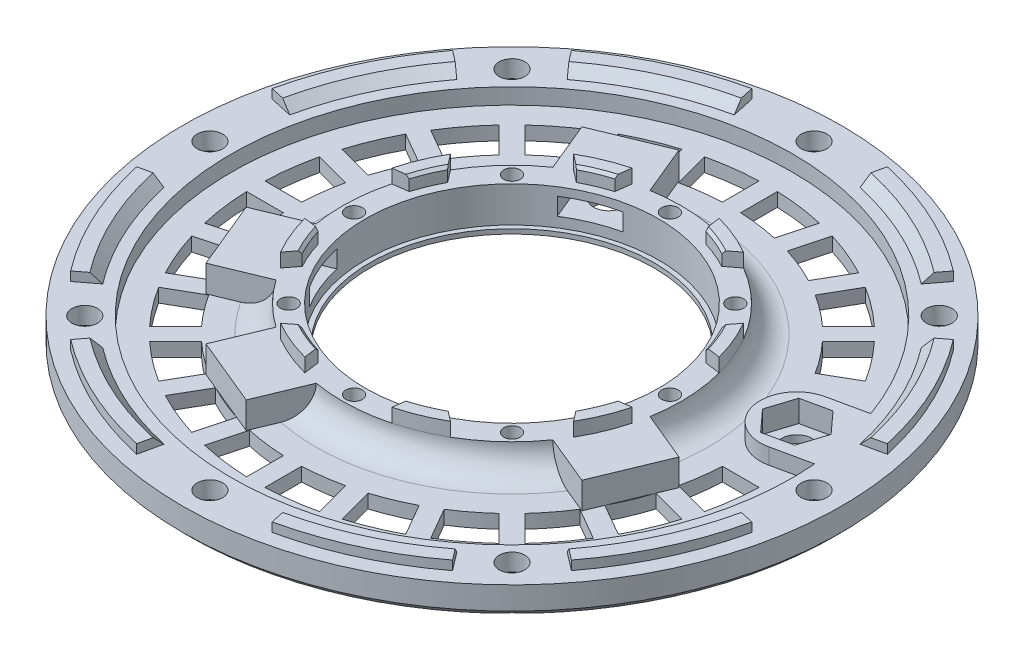
SolidWorks part; units mm, degrees
ref_plane "Front Plane" through (0, 0, 0) normal (0, 0, 1) x (1, 0, 0)
ref_plane "Top Plane" through (0, 0, 0) normal (0, 1, 0) x (1, 0, 0)
ref_plane "Right Plane" through (0, 0, 0) normal (1, 0, 0) x (0, 0, -1)
sketch "Sketch1" plane through (0, 0, 0) normal (0, 1, 0) x (1, 0, 0)
  circle A0 centre (0, 0) radius 16.025
  circle A1 centre (0, 0) radius 36
  dimension "D1" = 32.05
  dimension "D2" = 72
extrude "Boss-Extrude1" add sketch "Sketch1" along normal blind 1
sketch "Sketch2" plane through (0, 0, 0) normal (0, -1, 0) x (1, 0, 0)
  circle A0 centre (0, 0) radius 17.25 construction
  circle A1 centre (0, 0) radius 18.5 construction
  circle A2 centre (0, 0) radius 18.5
  circle A3 centre (0, 0) radius 16.025 construction
  circle A4 centre (0, 0) radius 16.025
  arc A5 (-1.2, 18.461) -> (-4.705, 17.8917) centre (0, 0) ccw construction
  point P3 (0, -17.25)
extrude "Boss-Extrude2" add sketch "Sketch2" against normal offset from surface (3.9 mm away) 3.9 up to face at (0, 0, 36)
fillet "Fillet1" radius 2.9 1 edges at (0, 1, 18.5)
sketch "Sketch4" plane through (0, 0, 0) normal (0, 1, 0) x (1, 0, 0)
  circle A0 centre (0, 0) radius 15.525
  circle A1 centre (0, 0) radius 36
  circle A2 centre (0, 0) radius 36
  circle A3 centre (0, 0) radius 16.025 construction
  dimension "D2" = 0.5
  dimension "D1" = 0
extrude "Boss-Extrude3" add sketch "Sketch4" against normal blind 0.5
sketch "Sketch5" plane through (0, 1, 0) normal (0, 1, 0) x (1, 0, 0)
  line L0 (27.99, -0.75) -> (19.9859, -0.75) construction
  line L1 (19.9859, 0.75) -> (27.99, 0.75) construction
  line L2 (27.99, -0.75) -> (19.9859, -0.75) construction
  line L3 (19.9859, 0.75) -> (27.99, 0.75) construction
  line L4 (0, 0) -> (36, 0) construction
  line L5 (0, 0) -> (34.7733, 9.3175) construction
  line L6 (34.7733, 9.3175) -> (36, 0) construction
  line L7 (0, 0) -> (35.3867, 4.6587) construction
  line L8 (27.99, 1) -> (23.9792, 1)
  line L9 (27.295, 6.2784) -> (23.4209, 5.2403)
  line L10 (27.99, -1) -> (23.9792, -1)
  line L11 (27.295, -6.2784) -> (23.4209, -5.2403)
  line L12 (26.7774, -8.2103) -> (22.9033, -7.1722)
  line L13 (24.74, -13.129) -> (21.2666, -11.1236)
  line L14 (23.74, -14.861) -> (20.2666, -12.8556)
  line L15 (20.499, -19.0848) -> (17.6629, -16.2487)
  line L16 (19.0848, -20.499) -> (16.2487, -17.6629)
  line L17 (14.861, -23.74) -> (12.8556, -20.2666)
  line L18 (13.129, -24.74) -> (11.1236, -21.2666)
  line L19 (8.2103, -26.7774) -> (7.1722, -22.9033)
  line L20 (6.2784, -27.295) -> (5.2403, -23.4209)
  line L21 (1, -27.99) -> (1, -23.9792)
  line L22 (-1, -27.99) -> (-1, -23.9792)
  line L23 (-6.2784, -27.295) -> (-5.2403, -23.4209)
  line L24 (-8.2103, -26.7774) -> (-7.1722, -22.9033)
  line L25 (-13.129, -24.74) -> (-11.1236, -21.2666)
  line L26 (-14.861, -23.74) -> (-12.8556, -20.2666)
  line L27 (-19.0848, -20.499) -> (-16.2487, -17.6629)
  line L28 (-20.499, -19.0848) -> (-17.6629, -16.2487)
  line L29 (-23.74, -14.861) -> (-20.2666, -12.8556)
  line L30 (-24.74, -13.129) -> (-21.2666, -11.1236)
  line L31 (-26.7774, -8.2103) -> (-22.9033, -7.1722)
  line L32 (-27.295, -6.2784) -> (-23.4209, -5.2403)
  line L33 (-27.99, -1) -> (-23.9792, -1)
  line L34 (-27.99, 1) -> (-23.9792, 1)
  line L35 (-27.295, 6.2784) -> (-23.4209, 5.2403)
  line L36 (-26.7774, 8.2103) -> (-22.9033, 7.1722)
  line L37 (-24.74, 13.129) -> (-21.2666, 11.1236)
  line L38 (-23.74, 14.861) -> (-20.2666, 12.8556)
  line L39 (-20.499, 19.0848) -> (-17.6629, 16.2487)
  line L40 (-19.0848, 20.499) -> (-16.2487, 17.6629)
  line L41 (-14.861, 23.74) -> (-12.8556, 20.2666)
  line L42 (-13.129, 24.74) -> (-11.1236, 21.2666)
  line L43 (-8.2103, 26.7774) -> (-7.1722, 22.9033)
  line L44 (-6.2784, 27.295) -> (-5.2403, 23.4209)
  line L45 (-1, 27.99) -> (-1, 23.9792)
  line L46 (1, 27.99) -> (1, 23.9792)
  line L47 (6.2784, 27.295) -> (5.2403, 23.4209)
  line L48 (8.2103, 26.7774) -> (7.1722, 22.9033)
  line L49 (13.129, 24.74) -> (11.1236, 21.2666)
  line L50 (14.861, 23.74) -> (12.8556, 20.2666)
  line L51 (19.0848, 20.499) -> (16.2487, 17.6629)
  line L52 (20.499, 19.0848) -> (17.6629, 16.2487)
  line L53 (23.74, 14.861) -> (20.2666, 12.8556)
  line L54 (24.74, 13.129) -> (21.2666, 11.1236)
  line L55 (26.7774, 8.2103) -> (22.9033, 7.1722)
  line L56 (0, 0) -> (23.9792, 1) construction
  circle A0 centre (0, 0) radius 24 construction
  circle A2 centre (0, 0) radius 36 construction
  arc A3 (23.9792, 1) -> (23.4209, 5.2403) centre (0, 0) ccw
  arc A4 (27.99, 1) -> (27.295, 6.2784) centre (0, 0) ccw
  arc A5 (27.295, -6.2784) -> (27.99, -1) centre (0, 0) ccw
  arc A6 (23.4209, -5.2403) -> (23.9792, -1) centre (0, 0) ccw
  arc A7 (24.74, -13.129) -> (26.7774, -8.2103) centre (0, 0) ccw
  arc A8 (21.2666, -11.1236) -> (22.9033, -7.1722) centre (0, 0) ccw
  arc A9 (20.499, -19.0848) -> (23.74, -14.861) centre (0, 0) ccw
  arc A10 (17.6629, -16.2487) -> (20.2666, -12.8556) centre (0, 0) ccw
  arc A11 (14.861, -23.74) -> (19.0848, -20.499) centre (0, 0) ccw
  arc A12 (12.8556, -20.2666) -> (16.2487, -17.6629) centre (0, 0) ccw
  arc A13 (8.2103, -26.7774) -> (13.129, -24.74) centre (0, 0) ccw
  arc A14 (7.1722, -22.9033) -> (11.1236, -21.2666) centre (0, 0) ccw
  arc A15 (1, -27.99) -> (6.2784, -27.295) centre (0, 0) ccw
  arc A16 (1, -23.9792) -> (5.2403, -23.4209) centre (0, 0) ccw
  arc A17 (-6.2784, -27.295) -> (-1, -27.99) centre (0, 0) ccw
  arc A18 (-5.2403, -23.4209) -> (-1, -23.9792) centre (0, 0) ccw
  arc A19 (-13.129, -24.74) -> (-8.2103, -26.7774) centre (0, 0) ccw
  arc A20 (-11.1236, -21.2666) -> (-7.1722, -22.9033) centre (0, 0) ccw
  arc A21 (-19.0848, -20.499) -> (-14.861, -23.74) centre (0, 0) ccw
  arc A22 (-16.2487, -17.6629) -> (-12.8556, -20.2666) centre (0, 0) ccw
  arc A23 (-23.74, -14.861) -> (-20.499, -19.0848) centre (0, 0) ccw
  arc A24 (-20.2666, -12.8556) -> (-17.6629, -16.2487) centre (0, 0) ccw
  arc A25 (-26.7774, -8.2103) -> (-24.74, -13.129) centre (0, 0) ccw
  arc A26 (-22.9033, -7.1722) -> (-21.2666, -11.1236) centre (0, 0) ccw
  arc A27 (-27.99, -1) -> (-27.295, -6.2784) centre (0, 0) ccw
  arc A28 (-23.9792, -1) -> (-23.4209, -5.2403) centre (0, 0) ccw
  arc A29 (-27.295, 6.2784) -> (-27.99, 1) centre (0, 0) ccw
  arc A30 (-23.4209, 5.2403) -> (-23.9792, 1) centre (0, 0) ccw
  arc A31 (-24.74, 13.129) -> (-26.7774, 8.2103) centre (0, 0) ccw
  arc A32 (-21.2666, 11.1236) -> (-22.9033, 7.1722) centre (0, 0) ccw
  arc A33 (-20.499, 19.0848) -> (-23.74, 14.861) centre (0, 0) ccw
  arc A34 (-17.6629, 16.2487) -> (-20.2666, 12.8556) centre (0, 0) ccw
  arc A35 (-14.861, 23.74) -> (-19.0848, 20.499) centre (0, 0) ccw
  arc A36 (-12.8556, 20.2666) -> (-16.2487, 17.6629) centre (0, 0) ccw
  arc A37 (-8.2103, 26.7774) -> (-13.129, 24.74) centre (0, 0) ccw
  arc A38 (-7.1722, 22.9033) -> (-11.1236, 21.2666) centre (0, 0) ccw
  arc A39 (-1, 27.99) -> (-6.2784, 27.295) centre (0, 0) ccw
  arc A40 (-1, 23.9792) -> (-5.2403, 23.4209) centre (0, 0) ccw
  arc A41 (6.2784, 27.295) -> (1, 27.99) centre (0, 0) ccw
  arc A42 (5.2403, 23.4209) -> (1, 23.9792) centre (0, 0) ccw
  arc A43 (13.129, 24.74) -> (8.2103, 26.7774) centre (0, 0) ccw
  arc A44 (11.1236, 21.2666) -> (7.1722, 22.9033) centre (0, 0) ccw
  arc A45 (19.0848, 20.499) -> (14.861, 23.74) centre (0, 0) ccw
  arc A46 (16.2487, 17.6629) -> (12.8556, 20.2666) centre (0, 0) ccw
  arc A47 (23.74, 14.861) -> (20.499, 19.0848) centre (0, 0) ccw
  arc A48 (20.2666, 12.8556) -> (17.6629, 16.2487) centre (0, 0) ccw
  arc A49 (26.7774, 8.2103) -> (24.74, 13.129) centre (0, 0) ccw
  arc A50 (22.9033, 7.1722) -> (21.2666, 11.1236) centre (0, 0) ccw
  dimension "D1" = 15
  dimension "D2" = 1
  dimension "D4" = 24
  dimension "D3" = 24
extrude "Cut-Extrude1" cut sketch "Sketch5" against normal through all both and the other way through all
sketch "Sketch7" plane through (0, 3.9, 0) normal (0, 1, 0) x (1, 0, 0)
  line L0 (0, 0) -> (0, 17.25) construction
  circle A0 centre (0, 17.25) radius 0.9
  circle A1 centre (12.1976, 12.1976) radius 0.9
  circle A2 centre (17.25, 0) radius 0.9
  circle A3 centre (12.1976, -12.1976) radius 0.9
  circle A4 centre (0, -17.25) radius 0.9
  circle A5 centre (-12.1976, -12.1976) radius 0.9
  circle A6 centre (-17.25, 0) radius 0.9
  circle A7 centre (-12.1976, 12.1976) radius 0.9
  point P21 (0, 0)
  dimension "D1" = 1.8
  dimension "D2" = 8
extrude "Cut-Extrude2" cut sketch "Sketch7" against normal through all
sketch "Sketch8" plane through (0, 1, 0) normal (0, 1, 0) x (1, 0, 0)
  arc A0 (-30.6392, -0.8144) -> (-29.9521, -6.5032) centre (0, 0) ccw construction
  arc A1 (-30.6392, -0.8144) -> (-29.9521, -6.5032) centre (0, 0) ccw construction
  arc A2 (-29.9521, 6.5032) -> (-30.6392, 0.8144) centre (0, 0) ccw construction
  arc A3 (-29.9521, 6.5032) -> (-30.6392, 0.8144) centre (0, 0) ccw construction
  circle A5 centre (0, 0) radius 30.65
  circle A6 centre (0, 0) radius 36 construction
  circle A7 centre (0, 0) radius 36
extrude "Boss-Extrude4" add sketch "Sketch8" along normal blind 1.7378
sketch "Sketch9" plane through (0, 2.7378, 0) normal (0, 1, 0) x (1, 0, 0)
  line L0 (0, 0) -> (-29.9521, 6.5032) construction
  line L1 (0, 0) -> (-29.9521, -6.5032) construction
  line L2 (-29.9521, 6.5032) -> (-29.9521, -6.5032) construction
  line L3 (-27.3707, 21.0023) -> (-23.9196, 18.3542) construction
  line L4 (0, 0) -> (0, 36) construction
  line L5 (0, 0) -> (-25.4558, 25.4558) construction
  line L6 (-24.3163, 18.6585) -> (0, 0) construction
  line L7 (-24.3163, 18.6585) -> (-28.5607, 21.9154) construction
  line L8 (-29.9521, 6.5032) -> (-35.1803, 7.6384) construction
  line L9 (-27.3521, 20.862) -> (-25.3687, 19.3401)
  line L10 (-31.2086, 14.47) -> (0, 0) construction
  line L11 (-33.5954, 7.3966) -> (-31.1523, 6.8662)
  line L12 (-7.3966, 33.5954) -> (-6.8662, 31.1523)
  line L13 (-20.862, 27.3521) -> (-19.3401, 25.3687)
  arc A0 (-29.9521, 6.5032) -> (-24.3163, 18.6585) centre (0, 0) cw construction
  arc A1 (-35.1803, 7.6384) -> (-28.5607, 21.9154) centre (0, 0) cw construction
  circle A2 centre (0, 0) radius 36 construction
  circle A3 centre (0, 0) radius 30.65 construction
  arc A4 (-27.2914, 20.9414) -> (-33.6168, 7.2989) centre (0, 0) ccw construction
  arc A5 (-31.1523, 6.8662) -> (-25.3687, 19.3401) centre (0, 0) cw
  arc A6 (-33.5954, 7.3966) -> (-27.3521, 20.862) centre (0, 0) cw
  circle A7 centre (0, 0) radius 36 construction
  arc A8 (-6.8662, 31.1523) -> (-19.3401, 25.3687) centre (0, 0) ccw
  arc A9 (-7.3966, 33.5954) -> (-20.862, 27.3521) centre (0, 0) ccw
  dimension "D2" = 0.1
  dimension "D3" = 45
  dimension "D4" = 0.1
  dimension "D1" = 2.5
extrude "Boss-Extrude5" add sketch "Sketch9" along normal blind 1
ref_axis "Axis1" through (0, -0.72, 0) along (0, 1, 0)
pattern_circular "CirPattern1" count 4 over 360 about axis through (0, -0.72, 0) along (0, 1, 0) of "Boss-Extrude5"
chamfer "Chamfer1" distance 1 angle 45 8 edges at (-28.9406, 3.7378, -13.4184) (-13.4184, 3.7378, -28.9406) (13.4184, 3.7378, -28.9406) (28.9406, 3.7378, -13.4184) (28.9406, 3.7378, 13.4184) (13.4184, 3.7378, 28.9406) (-13.4184, 3.7378, 28.9406) (-28.9406, 3.7378, 13.4184)
sketch "Sketch10" plane through (0, 2.7378, 0) normal (0, 1, 0) x (1, 0, 0)
  line L0 (0, 0) -> (0, 36) construction
  circle A0 centre (0, 0) radius 36 construction
  circle A1 centre (0, 33) radius 1.4 construction
  circle A2 centre (0, 33) radius 1.4
  circle A3 centre (23.3345, 23.3345) radius 1.4
  circle A4 centre (33, 0) radius 1.4
  circle A5 centre (23.3345, -23.3345) radius 1.4
  circle A6 centre (0, -33) radius 1.4
  circle A7 centre (-23.3345, -23.3345) radius 1.4
  circle A8 centre (-33, 0) radius 1.4
  circle A9 centre (-23.3345, 23.3345) radius 1.4
  point P26 (0, 0)
  dimension "D1" = 8
extrude "Cut-Extrude3" cut sketch "Sketch10" against normal through all both and the other way through all
chamfer "Chamfer2" distance 0.75 angle 45 1 edges at (0, -0.5, 36)
hole_wizard "CSK for M2.5 Flat Head Machine Screw1" positions "Sketch11" profile "Sketch12" countersink size "M2.5" standard "ANSI Metric" end condition through all
sketch "Sketch11" plane through (0, -0.5, 0) normal (0, -1, 0) x (-1, 0, 0)
  point P0 (0, -33)
  point P3 (23.3345, -23.3345)
  point P6 (33, 0)
  point P9 (23.3345, 23.3345)
  point P12 (0, 33)
  point P15 (-23.3345, 23.3345)
  point P18 (-33, 0)
  point P21 (-23.3345, -23.3345)
sketch "Sketch12" plane through (0, -0.5, 33) normal (1, 0, 0) x (0, 0, -1)
  line L0 (0, 0) -> (0, 4.4)
  line L1 (0, 4.4) -> (1.35, 4.4)
  line L2 (1.35, 4.4) -> (1.35, 1.4)
  line L3 (1.35, 1.4) -> (2.75, 0)
  line L5 (2.75, 0) -> (0, 0)
  line L6 (-1.35, 1.4) -> (-2.75, 0) construction
  line L11 (0, -6.35) -> (0, 107.95) construction
  dimension "Thru Hole Dia." = 2.7
  dimension "Thru Hole Depth" = 4.4
  dimension "Near C'Sink Dia." = 5.5
  dimension "Near C'Sink Angle" = 90
sketch "Sketch13" plane through (0, 3.9, 0) normal (0, 1, 0) x (1, 0, 0)
  line L0 (0, 0) -> (-7.0796, 17.0918) construction
  line L1 (0, 0) -> (0, 18.5) construction
  line L2 (-9.2808, 16.0037) -> (-7.9403, 14.9751)
  line L3 (-4.7538, 17.8788) -> (-4.9743, 16.2037)
  line L4 (4.7538, 17.8788) -> (4.9743, 16.2037)
  line L5 (9.2808, 16.0037) -> (7.9403, 14.9751)
  line L6 (16.0037, 9.2808) -> (14.9751, 7.9403)
  line L7 (17.8788, 4.7538) -> (16.2037, 4.9743)
  line L8 (17.8788, -4.7538) -> (16.2037, -4.9743)
  line L9 (16.0037, -9.2808) -> (14.9751, -7.9403)
  line L10 (9.2808, -16.0037) -> (7.9403, -14.9751)
  line L11 (4.7538, -17.8788) -> (4.9743, -16.2037)
  line L12 (-4.7538, -17.8788) -> (-4.9743, -16.2037)
  line L13 (-9.2808, -16.0037) -> (-7.9403, -14.9751)
  line L14 (-16.0037, -9.2808) -> (-14.9751, -7.9403)
  line L15 (-17.8788, -4.7538) -> (-16.2037, -4.9743)
  line L16 (-17.8788, 4.7538) -> (-16.2037, 4.9743)
  line L17 (-16.0037, 9.2808) -> (-14.9751, 7.9403)
  circle A0 centre (0, 0) radius 18.5 construction
  arc A1 (-7.9403, 14.9751) -> (-4.9743, 16.2037) centre (0, 0) cw
  arc A2 (-9.2808, 16.0037) -> (-4.7538, 17.8788) centre (0, 0) cw
  arc A3 (4.9743, 16.2037) -> (7.9403, 14.9751) centre (0, 0) cw
  arc A4 (4.7538, 17.8788) -> (9.2808, 16.0037) centre (0, 0) cw
  arc A5 (14.9751, 7.9403) -> (16.2037, 4.9743) centre (0, 0) cw
  arc A6 (16.0037, 9.2808) -> (17.8788, 4.7538) centre (0, 0) cw
  arc A7 (16.2037, -4.9743) -> (14.9751, -7.9403) centre (0, 0) cw
  arc A8 (17.8788, -4.7538) -> (16.0037, -9.2808) centre (0, 0) cw
  arc A9 (7.9403, -14.9751) -> (4.9743, -16.2037) centre (0, 0) cw
  arc A10 (9.2808, -16.0037) -> (4.7538, -17.8788) centre (0, 0) cw
  arc A11 (-4.9743, -16.2037) -> (-7.9403, -14.9751) centre (0, 0) cw
  arc A12 (-4.7538, -17.8788) -> (-9.2808, -16.0037) centre (0, 0) cw
  arc A13 (-14.9751, -7.9403) -> (-16.2037, -4.9743) centre (0, 0) cw
  arc A14 (-16.0037, -9.2808) -> (-17.8788, -4.7538) centre (0, 0) cw
  arc A15 (-16.2037, 4.9743) -> (-14.9751, 7.9403) centre (0, 0) cw
  arc A16 (-17.8788, 4.7538) -> (-16.0037, 9.2808) centre (0, 0) cw
  point P12 (-6.4865, 15.6598)
  point P20 (6.4865, 15.6598)
  point P25 (15.6598, 6.4865)
  point P30 (15.6598, -6.4865)
  point P35 (6.4865, -15.6598)
  point P40 (-6.4865, -15.6598)
  point P45 (-15.6598, -6.4865)
  point P50 (-15.6598, 6.4865)
  point P51 (0, 0)
  dimension "D1" = 22.5
  dimension "D2" = 30
  dimension "D3" = 1.55
  dimension "D4" = 4.9
  dimension "D5" = 8
extrude "Boss-Extrude6" add sketch "Sketch13" along normal blind 1.5
chamfer "Chamfer3" distance 0.3 angle 45 8 edges at (-15.6598, 5.4, -6.4865) (-15.6598, 5.4, 6.4865) (-6.4865, 5.4, 15.6598) (6.4865, 5.4, 15.6598) (15.6598, 5.4, 6.4865) (15.6598, 5.4, -6.4865) (6.4865, 5.4, -15.6598) (-6.4865, 5.4, -15.6598)
sketch "Sketch14" plane through (0, -0.5, 0) normal (0, -1, 0) x (1, 0, 0)
  line L0 (0, 0) -> (25.4558, -25.4558) construction
  line L1 (0, 0) -> (0, -36) construction
  line L6 (0, 0) -> (-22.1731, 9.1844) construction
  line L7 (0, 0) -> (-9.1844, -22.1731) construction
  circle A0 centre (0, 0) radius 36 construction
  arc A5 (-21.2666, 11.1236) -> (-22.9033, 7.1722) centre (0, 0) ccw construction
  circle A6 centre (-18.0157, 7.4623) radius 1.65
  circle A7 centre (-18.0157, 7.4623) radius 4.5 construction
  arc A8 (-11.1236, -21.2666) -> (-7.1722, -22.9033) centre (0, 0) ccw construction
  circle A9 centre (-7.4623, -18.0157) radius 1.65
  circle A10 centre (-7.4623, -18.0157) radius 4.5 construction
  circle A11 centre (18.0157, 7.4623) radius 1.65
  circle A12 centre (-7.4623, 18.0157) radius 1.65
  dimension "D2" = 3.3
  dimension "D3" = 9
  dimension "D1" = 45
sketch "Sketch15" plane through (0, 1, 0) normal (0, 1, 0) x (1, 0, 0)
  line L0 (-9.8825, 13.2519) -> (-12.8979, 20.5316)
  line L1 (-9.8825, 13.2519) -> (-2.3825, 16.3585)
  line L2 (-12.8979, 20.5316) -> (-5.3979, 23.6382)
  line L3 (-2.3825, 16.3585) -> (-5.3979, 23.6382)
  line L4 (-9.8825, 13.2519) -> (-5.3979, 23.6382) construction
  line L5 (-12.8979, 20.5316) -> (-2.3825, 16.3585) construction
  line L6 (0, 0) -> (-9.1844, 22.1731) construction
  line L7 (2.3825, 16.3585) -> (5.3979, 23.6382) [skipped]
  line L8 (2.3825, 16.3585) -> (9.8825, 13.2519) [skipped]
  line L9 (5.3979, 23.6382) -> (12.8979, 20.5316) [skipped]
  line L10 (9.8825, 13.2519) -> (12.8979, 20.5316) [skipped]
  line L11 (2.3825, 16.3585) -> (12.8979, 20.5316) construction
  line L12 (5.3979, 23.6382) -> (9.8825, 13.2519) construction
  line L13 (13.2519, 9.8825) -> (20.5316, 12.8979) [skipped]
  line L14 (13.2519, 9.8825) -> (16.3585, 2.3825) [skipped]
  line L15 (20.5316, 12.8979) -> (23.6382, 5.3979) [skipped]
  line L16 (16.3585, 2.3825) -> (23.6382, 5.3979) [skipped]
  line L17 (13.2519, 9.8825) -> (23.6382, 5.3979) construction
  line L18 (20.5316, 12.8979) -> (16.3585, 2.3825) construction
  line L19 (16.3585, -2.3825) -> (23.6382, -5.3979)
  line L20 (16.3585, -2.3825) -> (13.2519, -9.8825)
  line L21 (23.6382, -5.3979) -> (20.5316, -12.8979)
  line L22 (13.2519, -9.8825) -> (20.5316, -12.8979)
  line L23 (16.3585, -2.3825) -> (20.5316, -12.8979) construction
  line L24 (23.6382, -5.3979) -> (13.2519, -9.8825) construction
  line L25 (9.8825, -13.2519) -> (12.8979, -20.5316) [skipped]
  line L26 (9.8825, -13.2519) -> (2.3825, -16.3585) [skipped]
  line L27 (12.8979, -20.5316) -> (5.3979, -23.6382) [skipped]
  line L28 (2.3825, -16.3585) -> (5.3979, -23.6382) [skipped]
  line L29 (9.8825, -13.2519) -> (5.3979, -23.6382) construction
  line L30 (12.8979, -20.5316) -> (2.3825, -16.3585) construction
  line L31 (-2.3825, -16.3585) -> (-5.3979, -23.6382)
  line L32 (-2.3825, -16.3585) -> (-9.8825, -13.2519)
  line L33 (-5.3979, -23.6382) -> (-12.8979, -20.5316)
  line L34 (-9.8825, -13.2519) -> (-12.8979, -20.5316)
  line L35 (-2.3825, -16.3585) -> (-12.8979, -20.5316) construction
  line L36 (-5.3979, -23.6382) -> (-9.8825, -13.2519) construction
  line L37 (-13.2519, -9.8825) -> (-20.5316, -12.8979)
  line L38 (-13.2519, -9.8825) -> (-16.3585, -2.3825)
  line L39 (-20.5316, -12.8979) -> (-23.6382, -5.3979)
  line L40 (-16.3585, -2.3825) -> (-23.6382, -5.3979)
  line L41 (-13.2519, -9.8825) -> (-23.6382, -5.3979) construction
  line L42 (-20.5316, -12.8979) -> (-16.3585, -2.3825) construction
  line L43 (-16.3585, 2.3825) -> (-23.6382, 5.3979) [skipped]
  line L44 (-16.3585, 2.3825) -> (-13.2519, 9.8825) [skipped]
  line L45 (-23.6382, 5.3979) -> (-20.5316, 12.8979) [skipped]
  line L46 (-13.2519, 9.8825) -> (-20.5316, 12.8979) [skipped]
  line L47 (-16.3585, 2.3825) -> (-20.5316, 12.8979) construction
  line L48 (-23.6382, 5.3979) -> (-13.2519, 9.8825) construction
  line L49 (0, 0) -> (-9.1844, 22.1731) construction
  arc A1 (-7.1722, 22.9033) -> (-11.1236, 21.2666) centre (0, 0) ccw construction
  circle A2 centre (0, 0) radius 16.025 construction
  point P1 (-7.6402, 18.445)
  point P9 (7.6402, 18.445)
  point P18 (18.445, 7.6402)
  point P23 (18.445, -7.6402)
  point P28 (7.6402, -18.445)
  point P33 (-7.6402, -18.445)
  point P38 (-18.445, -7.6402)
  point P43 (-18.445, 7.6402)
  point P48 (0, 0)
  dimension "D1" = 7.5
  dimension "D2" = 8
extrude "Boss-Extrude7" add sketch "Sketch15" along normal up to surface (2.9 mm away) up to face at (0, 3.9, -16.35)
extrude "Cut-Extrude4" cut sketch "Sketch14" against normal blind 3.5
sketch "Sketch16" plane through (0, -0.5, 0) normal (0, -1, 0) x (1, 0, 0)
  line L0 (0, 0) -> (23.3345, -23.3345) construction
  line L1 (9.8544, 8.0903) -> (22.8679, -7.7606) construction
  line L2 (0, 0) -> (0, -17.25) construction
  line L3 (0, 0) -> (9.8544, 8.0903) construction
  line L4 (19.1824, 8.6291) -> (13.9057, 13.9057) construction
  line L5 (0, 0) -> (13.9057, 13.9057) construction
  line L6 (25.573, -5.5397) -> (28.0479, -3.0648) construction
  line L7 (28.0479, -3.0648) -> (12.4915, 12.4915) construction
  circle A0 centre (0, 0) radius 12.75 construction
  circle A1 centre (25.573, -5.5397) radius 1.65
  circle A2 centre (25.573, -5.5397) radius 3.5 construction
  circle A3 centre (18.0157, 7.4623) radius 1.65 construction
  dimension "D1" = 25.5
  dimension "D2" = 3.3
  dimension "D3" = 7
  dimension "D4" = 2
  dimension "D5" = 22
sketch "Sketch17" plane through (0, -0.5, 0) normal (0, -1, 0) x (1, 0, 0)
  line L0 (24.74, -13.129) -> (21.2666, -11.1236) construction
  line L1 (24.74, -13.129) -> (21.2666, -11.1236)
  arc A0 (21.2666, -11.1236) -> (22.9033, -7.1722) centre (0, 0) ccw construction
  arc A1 (24.74, -13.129) -> (26.7774, -8.2103) centre (0, 0) ccw construction
  arc A4 (21.2666, -11.1236) -> (22.1079, -9.3403) centre (0, 0) ccw
  arc A5 (24.74, -13.129) -> (25.8946, -10.6727) centre (0, 0) ccw
  arc A8 (25.8946, -10.6727) -> (22.1079, -9.3403) centre (25.573, -5.5397) ccw
extrude "Boss-Extrude8" add sketch "Sketch17" against normal up to surface (1.5 mm away) up to face at (25.7264, 1, -3.3869)
sketch "Sketch18" plane through (0, 1, 0) normal (0, 1, 0) x (1, 0, 0)
  line L0 (0, 0) -> (25.573, 5.5397) construction
  line L1 (24.7261, 9.449) -> (28.8522, 10.3429)
  line L2 (26.4198, 1.6304) -> (30.5459, 2.5242)
  arc A0 (24.7261, 9.449) -> (26.4198, 1.6304) centre (25.573, 5.5397) ccw
  circle A1 centre (0, 0) radius 30.65 construction
  circle A2 centre (0, 0) radius 30.65 construction
  arc A3 (30.5459, 2.5242) -> (28.8522, 10.3429) centre (0, 0) ccw
  dimension "D1" = 8
extrude "Boss-Extrude9" add sketch "Sketch18" along normal up to surface (1.7378 mm away) up to face at (0, 2.7378, -31.6)
extrude "Cut-Extrude5" cut sketch "Sketch16" against normal through all
sketch "Sketch19" plane through (0, 2.7378, 0) normal (0, 1, 0) x (1, 0, 0)
  line L0 (0, 0) -> (25.573, 5.5397) construction
  line L1 (28.6482, 6.2059) -> (26.5337, 8.536)
  line L2 (26.5337, 8.536) -> (23.4584, 7.8699)
  line L3 (23.4584, 7.8699) -> (22.4977, 4.8736)
  line L4 (22.4977, 4.8736) -> (24.6123, 2.5434)
  line L5 (24.6123, 2.5434) -> (27.6875, 3.2096)
  line L6 (27.6875, 3.2096) -> (28.6482, 6.2059)
  circle A0 centre (25.573, 5.5397) radius 2.725 construction
  dimension "D1" = 5.45
extrude "Cut-Extrude6" cut sketch "Sketch19" against normal blind 2.4
sketch "Sketch20" plane through (0, 3, 0) normal (0, -1, 0) x (1, 0, 0)
  line L0 (0, 0) -> (-18.0157, 7.4623) construction
  line L1 (-21.6087, 5.974) -> (-16.5274, 3.8693)
  line L2 (-21.6087, 5.974) -> (-19.5039, 11.0554)
  line L3 (-16.5274, 3.8693) -> (-14.4226, 8.9506) construction
  line L4 (-19.5039, 11.0554) -> (-14.4226, 8.9506)
  line L5 (-21.6087, 5.974) -> (-14.4226, 8.9506) construction
  line L6 (-16.5274, 3.8693) -> (-19.5039, 11.0554) construction
  line L7 (-14.4226, 8.9506) -> (-13.064, 8.3879)
  line L8 (-13.064, 8.3879) -> (-15.1688, 3.3065)
  line L9 (-15.1688, 3.3065) -> (-16.5274, 3.8693)
  line L10 (-8.3879, 13.064) -> (-8.9506, 14.4226)
  line L11 (-11.0554, 19.5039) -> (-8.9506, 14.4226)
  line L12 (-11.0554, 19.5039) -> (-5.974, 21.6087)
  line L13 (-5.974, 21.6087) -> (-3.8693, 16.5274)
  line L14 (-3.8693, 16.5274) -> (-3.3065, 15.1688)
  line L15 (-3.3065, 15.1688) -> (-8.3879, 13.064)
  line L16 (3.3065, 15.1688) -> (3.8693, 16.5274) [skipped]
  line L17 (5.974, 21.6087) -> (3.8693, 16.5274) [skipped]
  line L18 (5.974, 21.6087) -> (11.0554, 19.5039) [skipped]
  line L19 (11.0554, 19.5039) -> (8.9506, 14.4226) [skipped]
  line L20 (8.9506, 14.4226) -> (8.3879, 13.064) [skipped]
  line L21 (8.3879, 13.064) -> (3.3065, 15.1688) [skipped]
  line L22 (13.064, 8.3879) -> (14.4226, 8.9506)
  line L23 (19.5039, 11.0554) -> (14.4226, 8.9506)
  line L24 (19.5039, 11.0554) -> (21.6087, 5.974)
  line L25 (21.6087, 5.974) -> (16.5274, 3.8693)
  line L26 (16.5274, 3.8693) -> (15.1688, 3.3065)
  line L27 (15.1688, 3.3065) -> (13.064, 8.3879)
  line L28 (15.1688, -3.3065) -> (16.5274, -3.8693) [skipped]
  line L29 (21.6087, -5.974) -> (16.5274, -3.8693) [skipped]
  line L30 (21.6087, -5.974) -> (19.5039, -11.0554) [skipped]
  line L31 (19.5039, -11.0554) -> (14.4226, -8.9506) [skipped]
  line L32 (14.4226, -8.9506) -> (13.064, -8.3879) [skipped]
  line L33 (13.064, -8.3879) -> (15.1688, -3.3065) [skipped]
  line L34 (8.3879, -13.064) -> (8.9506, -14.4226) [skipped]
  line L35 (11.0554, -19.5039) -> (8.9506, -14.4226) [skipped]
  line L36 (11.0554, -19.5039) -> (5.974, -21.6087) [skipped]
  line L37 (5.974, -21.6087) -> (3.8693, -16.5274) [skipped]
  line L38 (3.8693, -16.5274) -> (3.3065, -15.1688) [skipped]
  line L39 (3.3065, -15.1688) -> (8.3879, -13.064) [skipped]
  line L40 (-3.3065, -15.1688) -> (-3.8693, -16.5274)
  line L41 (-5.974, -21.6087) -> (-3.8693, -16.5274)
  line L42 (-5.974, -21.6087) -> (-11.0554, -19.5039)
  line L43 (-11.0554, -19.5039) -> (-8.9506, -14.4226)
  line L44 (-8.9506, -14.4226) -> (-8.3879, -13.064)
  line L45 (-8.3879, -13.064) -> (-3.3065, -15.1688)
  line L46 (-13.064, -8.3879) -> (-14.4226, -8.9506) [skipped]
  line L47 (-19.5039, -11.0554) -> (-14.4226, -8.9506) [skipped]
  line L48 (-19.5039, -11.0554) -> (-21.6087, -5.974) [skipped]
  line L49 (-21.6087, -5.974) -> (-16.5274, -3.8693) [skipped]
  line L50 (-16.5274, -3.8693) -> (-15.1688, -3.3065) [skipped]
  line L51 (-15.1688, -3.3065) -> (-13.064, -8.3879) [skipped]
  circle A0 centre (0, 0) radius 15.525 construction
  point P57 (0, 0)
  dimension "D1" = 5.5
  dimension "D2" = 8
extrude "Cut-Extrude7" cut sketch "Sketch20" along normal blind 1.9
